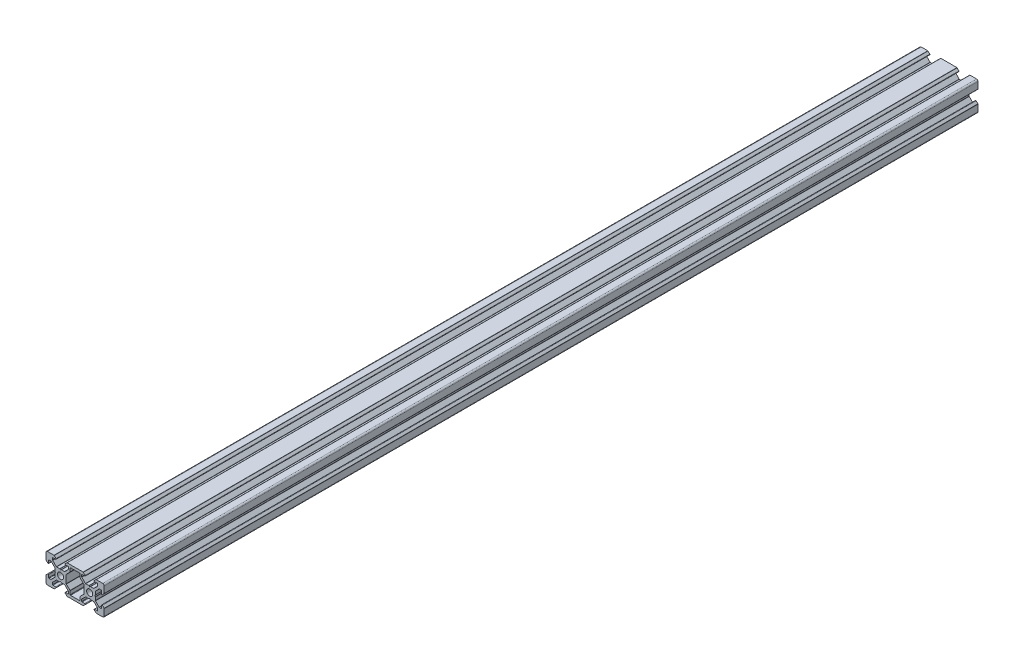
SolidWorks part; units mm, degrees
material "АД31Т ГОСТ 4784-97"
ref_plane "Спереди" through (0, 0, 0) normal (0, 0, 1) x (1, 0, 0)
ref_plane "Сверху" through (0, 0, 0) normal (0, 1, 0) x (1, 0, 0)
ref_plane "Справа" through (0, 0, 0) normal (1, 0, 0) x (0, 0, -1)
sketch "Эскиз1" plane through (0, 0, 0) normal (0, 0, 1) x (1, 0, 0)
  line L0 (12.9654, 0) -> (-12.9654, 0) construction
  line L1 (0, -12.9654) -> (0, 12.9654) construction
  line L2 (0, 0) -> (-18.3359, -18.3359) construction
  line L3 (-10, -10) -> (-10, -4.4)
  line L4 (-10, -4.4) -> (-8.2, -2.6)
  line L5 (-8.2, -2.6) -> (-8.2, -5.4993)
  line L6 (-8.2, -5.4993) -> (-6.56, -5.4993)
  line L7 (-6.56, -5.4993) -> (-3.9007, -2.84)
  line L8 (-3.9007, -2.84) -> (-3.9007, -0.5)
  line L9 (-3.9007, -0.5) -> (-3.4007, 0)
  line L10 (-0.5, -3.9007) -> (0, -3.4007)
  line L11 (-2.84, -3.9007) -> (-0.5, -3.9007)
  line L12 (-5.4993, -6.56) -> (-2.84, -3.9007)
  line L13 (-5.4993, -8.2) -> (-5.4993, -6.56)
  line L14 (-2.6, -8.2) -> (-5.4993, -8.2)
  line L15 (-4.4, -10) -> (-2.6, -8.2)
  line L16 (-10, -10) -> (-4.4, -10)
  line L17 (-10, 10) -> (-4.4, 10)
  line L18 (-4.4, 10) -> (-2.6, 8.2)
  line L19 (-2.6, 8.2) -> (-5.4993, 8.2)
  line L20 (-5.4993, 8.2) -> (-5.4993, 6.56)
  line L21 (-5.4993, 6.56) -> (-2.84, 3.9007)
  line L22 (-2.84, 3.9007) -> (-0.5, 3.9007)
  line L23 (-0.5, 3.9007) -> (0, 3.4007)
  line L24 (-3.9007, 0.5) -> (-3.4007, 0)
  line L25 (-3.9007, 2.84) -> (-3.9007, 0.5)
  line L26 (-6.56, 5.4993) -> (-3.9007, 2.84)
  line L27 (-8.2, 5.4993) -> (-6.56, 5.4993)
  line L28 (-8.2, 2.6) -> (-8.2, 5.4993)
  line L29 (-10, 4.4) -> (-8.2, 2.6)
  line L30 (-10, 10) -> (-10, 4.4)
  line L31 (0.5, 3.9007) -> (0, 3.4007)
  line L32 (0.5, -3.9007) -> (0, -3.4007)
  line L33 (10, -10) -> (10, 10) construction
  line L34 (3.9007, -0.5) -> (3.9007, 0.5)
  line L35 (6.56, -5.4993) -> (6.56, -8.2)
  line L36 (13.44, -5.4993) -> (16.0993, -2.84)
  line L37 (6.56, 5.4993) -> (3.9007, 2.84)
  line L38 (3.9007, 2.84) -> (3.9007, 0.5)
  line L39 (6.56, -8.2) -> (13.44, -8.2)
  line L40 (2.84, 3.9007) -> (0.5, 3.9007)
  line L41 (5.4993, 6.56) -> (2.84, 3.9007)
  line L42 (5.4993, 8.2) -> (5.4993, 6.56)
  line L43 (2.6, 8.2) -> (5.4993, 8.2)
  line L44 (4.4, 10) -> (2.6, 8.2)
  line L45 (15.6, 10) -> (4.4, 10)
  line L46 (15.6, -10) -> (4.4, -10)
  line L47 (4.4, -10) -> (2.6, -8.2)
  line L48 (2.6, -8.2) -> (5.4993, -8.2)
  line L49 (5.4993, -8.2) -> (5.4993, -6.56)
  line L50 (5.4993, -6.56) -> (2.84, -3.9007)
  line L51 (2.84, -3.9007) -> (0.5, -3.9007)
  line L52 (6.56, 5.4993) -> (6.56, 8.2)
  line L53 (3.9007, -2.84) -> (3.9007, -0.5)
  line L54 (6.56, -5.4993) -> (3.9007, -2.84)
  line L55 (16.0993, -2.84) -> (16.0993, -0.5)
  line L56 (6.56, 8.2) -> (13.44, 8.2)
  line L57 (13.44, 5.4993) -> (13.44, 8.2)
  line L58 (17.16, -3.9007) -> (19.5, -3.9007)
  line L59 (14.5007, -6.56) -> (17.16, -3.9007)
  line L60 (14.5007, -8.2) -> (14.5007, -6.56)
  line L61 (17.4, -8.2) -> (14.5007, -8.2)
  line L62 (15.6, -10) -> (17.4, -8.2)
  line L63 (15.6, 10) -> (17.4, 8.2)
  line L64 (17.4, 8.2) -> (14.5007, 8.2)
  line L65 (14.5007, 8.2) -> (14.5007, 6.56)
  line L66 (14.5007, 6.56) -> (17.16, 3.9007)
  line L67 (17.16, 3.9007) -> (19.5, 3.9007)
  line L68 (16.0993, 2.84) -> (16.0993, 0.5)
  line L69 (13.44, 5.4993) -> (16.0993, 2.84)
  line L70 (13.44, -5.4993) -> (13.44, -8.2)
  line L71 (16.0993, -0.5) -> (16.0993, 0.5)
  line L72 (19.5, -3.9007) -> (20, -3.4007)
  line L73 (19.5, 3.9007) -> (20, 3.4007)
  line L74 (30, 10) -> (30, 4.4)
  line L75 (30, 4.4) -> (28.2, 2.6)
  line L76 (28.2, 2.6) -> (28.2, 5.4993)
  line L77 (28.2, 5.4993) -> (26.56, 5.4993)
  line L78 (26.56, 5.4993) -> (23.9007, 2.84)
  line L79 (23.9007, 2.84) -> (23.9007, 0.5)
  line L80 (23.9007, 0.5) -> (23.4007, 0)
  line L81 (20.5, 3.9007) -> (20, 3.4007)
  line L82 (22.84, 3.9007) -> (20.5, 3.9007)
  line L83 (25.4993, 6.56) -> (22.84, 3.9007)
  line L84 (25.4993, 8.2) -> (25.4993, 6.56)
  line L85 (22.6, 8.2) -> (25.4993, 8.2)
  line L86 (24.4, 10) -> (22.6, 8.2)
  line L87 (30, 10) -> (24.4, 10)
  line L88 (30, -10) -> (24.4, -10)
  line L89 (24.4, -10) -> (22.6, -8.2)
  line L90 (22.6, -8.2) -> (25.4993, -8.2)
  line L91 (25.4993, -8.2) -> (25.4993, -6.56)
  line L92 (25.4993, -6.56) -> (22.84, -3.9007)
  line L93 (22.84, -3.9007) -> (20.5, -3.9007)
  line L94 (20.5, -3.9007) -> (20, -3.4007)
  line L95 (23.9007, -0.5) -> (23.4007, 0)
  line L96 (23.9007, -2.84) -> (23.9007, -0.5)
  line L97 (26.56, -5.4993) -> (23.9007, -2.84)
  line L98 (28.2, -5.4993) -> (26.56, -5.4993)
  line L99 (28.2, -2.6) -> (28.2, -5.4993)
  line L100 (30, -4.4) -> (28.2, -2.6)
  line L101 (30, -10) -> (30, -4.4)
  circle A0 centre (0, 0) radius 2.1
  circle A1 centre (20, 0) radius 2.1
  point P62 (10, 8.2)
  point P80 (10, -8.2)
  dimension "D5" = 2.6
  dimension "D10" = 4.2
  dimension "D2" = 10
  dimension "D3" = 1.64
  dimension "D4" = 1.5
  dimension "D6" = 1.8
  dimension "D7" = 2.84
  dimension "D8" = 0.5
  dimension "D9" = 45
extrude "Бобышка-Вытянуть1" add sketch "Эскиз1" along normal up to surface (600 mm away)
fillet "Скругление1" radius 1 4 edges at (-10, 10, 300) (-10, -10, 300) (30, 10, 300) (30, -10, 300)
fillet "Скругление2" radius 0.3 83 edges at (-4.4, 10, 300) (-2.6, 8.2, 300) (-5.4993, 8.2, 300) (-5.4993, 6.56, 300) (-2.84, 3.9007, 300) (-0.5, 3.9007, 300) (0.5, 3.9007, 300) (2.84, 3.9007, 300) (5.4993, 6.56, 300) (4.4, 10, 300) (5.4993, 8.2, 300) (2.6, 8.2, 300) (3.9007, 2.84, 300) (3.9007, -2.84, 300) (4.4, -10, 300) (2.6, -8.2, 300) (5.4993, -8.2, 300) (5.4993, -6.56, 300) (2.84, -3.9007, 300) (0.5, -3.9007, 300) (-0.5, -3.9007, 300) (-2.84, -3.9007, 300) (-5.4993, -6.56, 300) (-5.4993, -8.2, 300) (-2.6, -8.2, 300) (-10, -4.4, 300) (-8.2, -2.6, 300) (-8.2, -5.4993, 300) (-6.56, -5.4993, 300) (-3.9007, -2.84, 300) (-3.9007, -0.5, 300) (-3.9007, 0.5, 300) (-3.9007, 2.84, 300) (-6.56, 5.4993, 300) (-8.2, 5.4993, 300) (-8.2, 2.6, 300) (-10, 4.4, 300) (6.56, -5.4993, 300) (6.56, 5.4993, 300) (6.56, 8.2, 300) (13.44, 8.2, 300) (13.44, 5.4993, 300) (16.0993, 2.84, 300) (16.0993, -2.84, 300) (13.44, -5.4993, 300) (13.44, -8.2, 300) (6.56, -8.2, 300) (15.6, 10, 300) (17.4, 8.2, 300) (14.5007, 8.2, 300) (14.5007, 6.56, 300) (17.16, 3.9007, 300) (19.5, 3.9007, 300) (20.5, 3.9007, 300) (22.84, 3.9007, 300) (25.4993, 6.56, 300) (25.4993, 8.2, 300) (22.6, 8.2, 300) (24.4, 10, 300) (30, 4.4, 300) (28.2, 2.6, 300) (28.2, 5.4993, 300) (26.56, 5.4993, 300) (23.9007, 2.84, 300) (23.9007, 0.5, 300) (23.9007, -0.5, 300) (23.9007, -2.84, 300) (26.56, -5.4993, 300) (28.2, -5.4993, 300) (28.2, -2.6, 300) (30, -4.4, 300) (24.4, -10, 300) (22.6, -8.2, 300) (25.4993, -8.2, 300) (25.4993, -6.56, 300) (22.84, -3.9007, 300) (20.5, -3.9007, 300) (19.5, -3.9007, 300) (17.16, -3.9007, 300) (14.5007, -6.56, 300) (14.5007, -8.2, 300) (17.4, -8.2, 300) (15.6, -10, 300)
